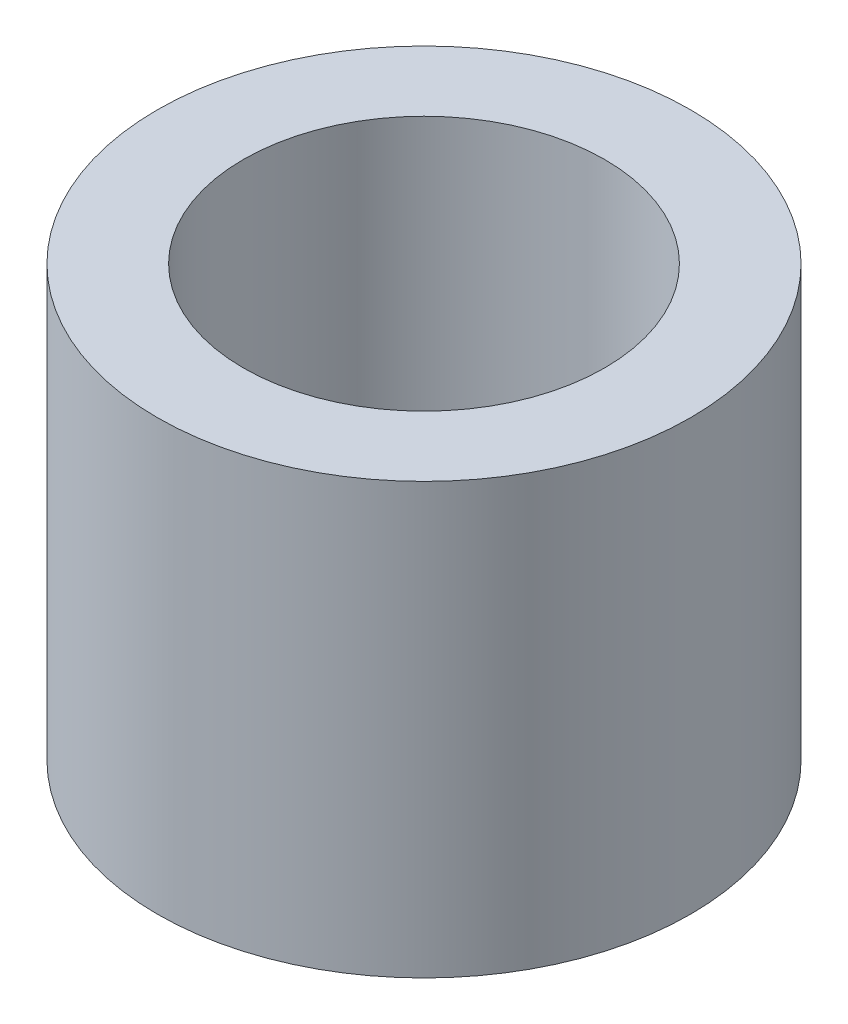
SolidWorks part; units mm, degrees
ref_plane "Front Plane" through (0, 0, 0) normal (0, 0, 1) x (1, 0, 0)
ref_plane "Top Plane" through (0, 0, 0) normal (0, 1, 0) x (1, 0, 0)
ref_plane "Right Plane" through (0, 0, 0) normal (1, 0, 0) x (0, 0, -1)
sketch "Sketch1" plane through (0, 0, 0) normal (0, 1, 0) x (1, 0, 0)
  circle A0 centre (0, 0) radius 2.1
  circle A1 centre (0, 0) radius 3.1
  dimension "D1" = 6.2
  dimension "D2" = 4.2
extrude "Boss-Extrude1" add sketch "Sketch1" along normal blind 5
equation "\"ID\"= 4.2mm"
equation "\"D2@Sketch1\"=\"ID\""
equation "\"Height\"= 5mm"
equation "\"D1@Boss-Extrude1\"=\"Height\""
